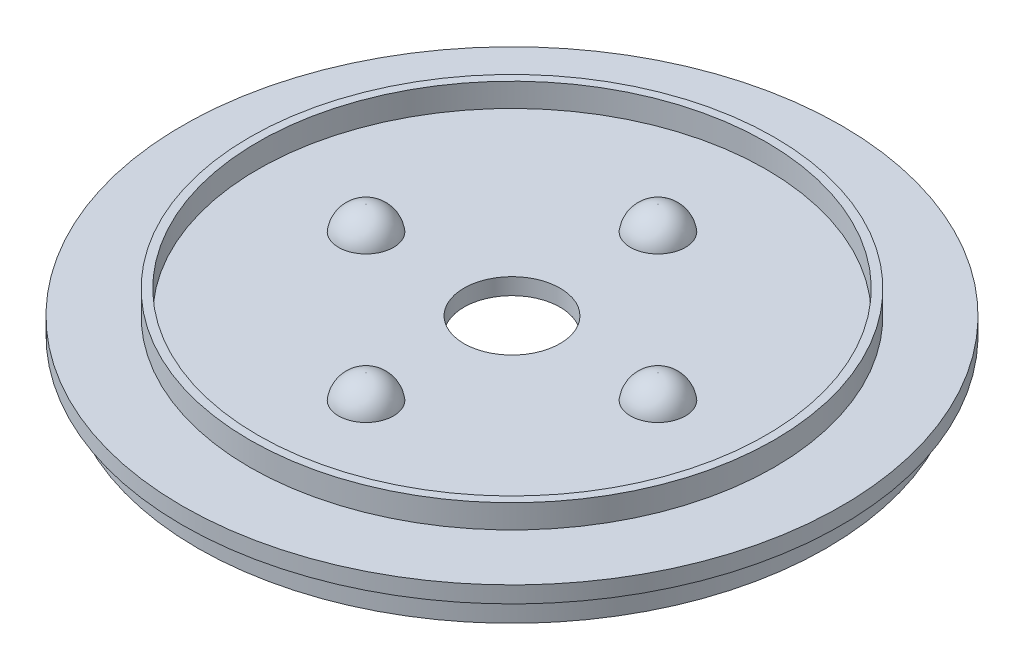
SolidWorks part; units mm, degrees
material "ABS"
ref_plane "Front Plane" through (0, 0, 0) normal (0, 0, 1) x (1, 0, 0)
ref_plane "Top Plane" through (0, 0, 0) normal (0, 1, 0) x (1, 0, 0)
ref_plane "Right Plane" through (0, 0, 0) normal (1, 0, 0) x (0, 0, -1)
sketch "Sketch3" plane through (0, 0, 0) normal (0, 1, 0) x (1, 0, 0)
  circle A0 centre (0, 0) radius 60
  circle A1 centre (0, 0) radius 8.75
  dimension "D1" = 120
  dimension "D2" = 17.5
extrude "Boss-Extrude1" add sketch "Sketch3" along normal blind 3
sketch "Sketch4" plane through (0, 0, 0) normal (0, -1, 0) x (1, 0, 0)
  circle A0 centre (0, 0) radius 57.25
  circle A1 centre (0, 0) radius 55.75
  dimension "D1" = 114.5
  dimension "D2" = 111.5
extrude "Boss-Extrude2" add sketch "Sketch4" along normal blind 5
sketch "Sketch5" plane through (0, 0, 0) normal (0, -1, 0) x (1, 0, 0)
  circle A0 centre (0, 0) radius 22
  circle A1 centre (0, 0) radius 20.5
  dimension "D1" = 44
  dimension "D2" = 41
extrude "Boss-Extrude3" add sketch "Sketch5" along normal blind 7
sketch "Sketch6" plane through (0, 3, 0) normal (0, 1, 0) x (1, 0, 0)
  circle A0 centre (0, 0) radius 47.75
  circle A1 centre (0, 0) radius 46.25
  dimension "D1" = 95.5
  dimension "D2" = 92.5
extrude "Boss-Extrude4" add sketch "Sketch6" along normal blind 4.3
sketch "Sketch10" plane through (0, 3, 0) normal (0, 1, 0) x (1, 0, 0)
  line L0 (0, 18.6634) -> (0, 34.4865) construction
  circle A0 centre (0, 26.575) radius 5
  circle A2 centre (26.575, 0) radius 5
  circle A3 centre (0, -26.575) radius 5
  circle A4 centre (-26.575, 0) radius 5
  point P16 (0, 0)
  dimension "D1" = 10
  dimension "D2" = 4
extrude "Boss-Extrude5" add sketch "Sketch10" along normal up to surface (4.3 mm away) up to face at (0, 7.3, 47.75)
fillet "Fillet2" radius 5 4 edges at (0, 7.3, 31.575) (26.575, 7.3, 5) (0, 7.3, -21.575) (-26.575, 7.3, 5)
